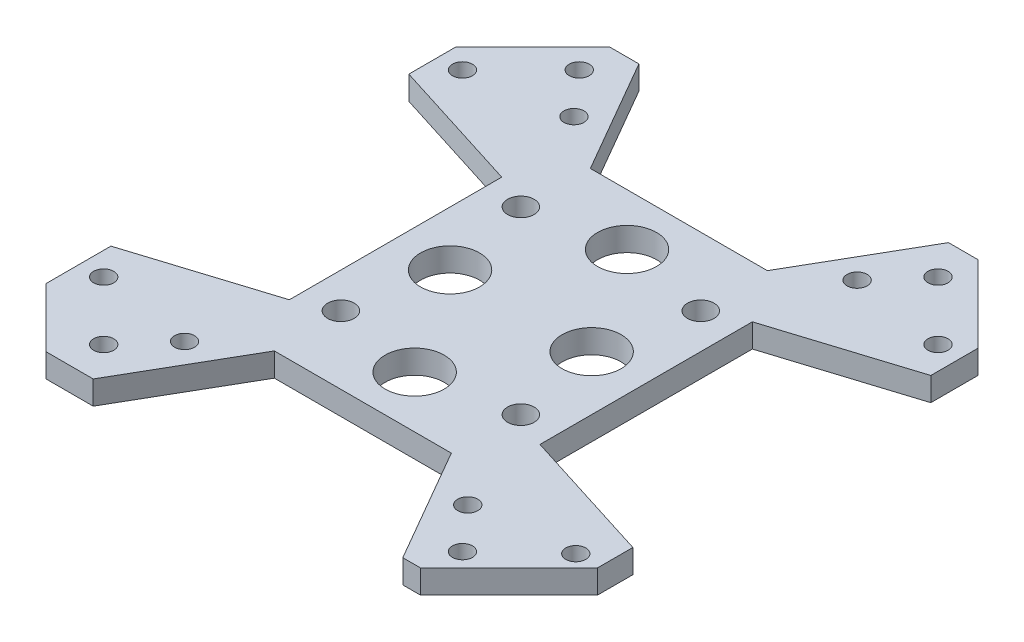
SolidWorks part; units mm, degrees
material "Thornel Mat VMA"
ref_plane "前视基准面" through (0, 0, 0) normal (0, 0, 1) x (1, 0, 0)
ref_plane "上视基准面" through (0, 0, 0) normal (0, 1, 0) x (1, 0, 0)
ref_plane "右视基准面" through (0, 0, 0) normal (1, 0, 0) x (0, 0, -1)
other "Configuration Table"
sketch "草图1" plane through (0, 0, 0) normal (0, 1, 0) x (1, 0, 0)
  line L8 (-40.3051, 30.4056) -> (-30.4056, 40.3051) construction
  line L9 (0, 0) -> (75.4458, 0) construction
  line L10 (0, 0) -> (0, 38.6741) construction
  line L21 (44.2385, 33.25) -> (44.2385, 25.25)
  line L22 (-44.2385, 33.25) -> (-44.2385, 25.25)
  line L23 (-34.2385, -46.25) -> (-26.2385, -46.25)
  line L24 (-31.2385, 46.25) -> (-26.2385, 46.25)
  line L25 (-44.2385, 33.25) -> (-31.2385, 46.25)
  line L26 (31.2385, 46.25) -> (44.2385, 33.25)
  line L27 (29.2385, -46.25) -> (44.2385, -31.25)
  line L28 (-44.2385, -36.25) -> (-34.2385, -46.25)
  line L30 (-21.2385, 18) -> (-21.2385, -18)
  line L32 (-44.2385, -25.25) -> (-44.2385, -36.25)
  line L33 (-44.2385, 25.25) -> (-21.2385, 18)
  line L34 (-44.2385, -25.25) -> (-21.2385, -18)
  line L35 (44.2385, -25.25) -> (21.2385, -18)
  line L36 (21.2385, 18) -> (21.2385, -18)
  line L37 (44.2385, 25.25) -> (21.2385, 18)
  line L38 (44.2385, -25.25) -> (44.2385, -31.25)
  line L39 (-26.2385, 46.25) -> (-15, 26.7844)
  line L40 (-15, 26.7844) -> (15, 26.7844)
  line L41 (26.2385, 46.25) -> (15, 26.7844)
  line L42 (26.2385, 46.25) -> (31.2385, 46.25)
  line L43 (26.2385, -46.25) -> (15, -26.7844)
  line L44 (-15, -26.7844) -> (15, -26.7844)
  line L45 (-26.2385, -46.25) -> (-15, -26.7844)
  line L46 (26.2385, -46.25) -> (29.2385, -46.25)
  circle A0 centre (-15.25, -15.25) radius 2.25
  circle A1 centre (-15.25, 15.25) radius 2.25
  circle A2 centre (15.25, -15.25) radius 2.25
  circle A3 centre (15.25, 15.25) radius 2.25
  circle A4 centre (-24, -33) radius 1.7
  circle A9 centre (-12, 0) radius 5
  circle A10 centre (0, 18) radius 5
  circle A13 centre (-30.4056, -40.3051) radius 1.7
  circle A14 centre (-30.4056, 40.3051) radius 1.7
  circle A15 centre (-40.3051, 30.4056) radius 1.7
  circle A16 centre (30.4056, -40.3051) radius 1.7
  circle A17 centre (40.3051, -31) radius 1.6949
  circle A18 centre (40.3051, 30.4056) radius 1.6949
  circle A19 centre (30.4056, 40.3051) radius 1.7
  circle A20 centre (-40.3051, -30.4056) radius 1.7
  circle A21 centre (24, -33) radius 1.7
  circle A22 centre (24, 33) radius 1.7
  circle A23 centre (-24, 33) radius 1.7
  circle A24 centre (12, 0) radius 5
  circle A25 centre (0, -18) radius 5
  point P1 (-44.2385, -46.25)
  point P7 (-44.2385, 46.25)
  point P57 (44.2385, 46.25)
  point P58 (44.2385, -46.25)
  point P61 (-21.2385, 0)
  point P70 (0, 26.7844)
  dimension "D3" = 4.5
  dimension "D4" = 4.5
  dimension "D14" = 3.4
  dimension "D21" = 10
  dimension "D22" = 10
  dimension "D2" = 46.25
  dimension "D5" = 44.2385
  dimension "D6" = 60
  dimension "D7" = 23
  dimension "D9" = 18
  dimension "D10" = 12
  dimension "D11" = 40.3051
  dimension "D12" = 24
  dimension "D13" = 33
  dimension "D17" = 8
  dimension "D18" = 18
  dimension "D19" = 5
  dimension "D20" = 15
extrude "凸台-拉伸1" add sketch "草图1" along normal blind 4
